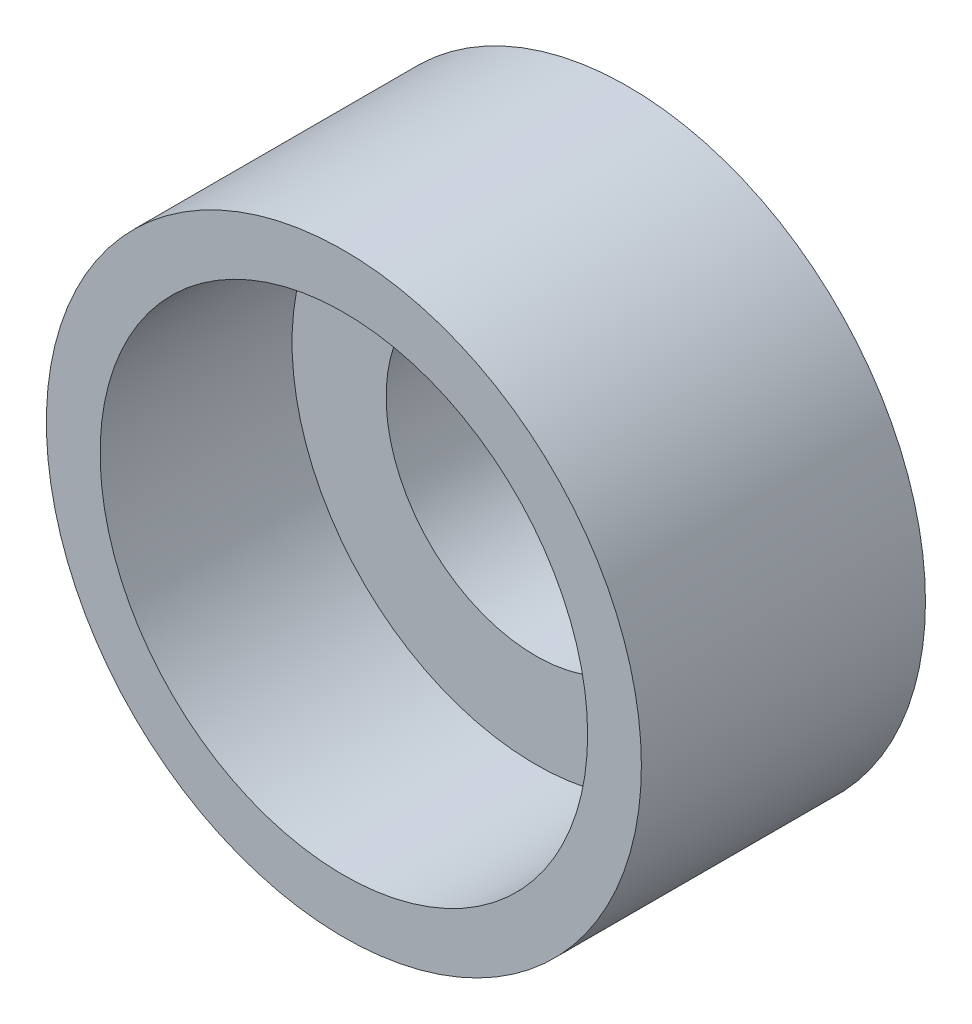
SolidWorks part; units mm, degrees
ref_plane "Front Plane" through (0, 0, 0) normal (1, 0, 0) x (0, 1, 0)
ref_plane "Top Plane" through (0, 0, 0) normal (0, 0, 1) x (0, 1, 0)
ref_plane "Right Plane" through (0, 0, 0) normal (0, 1, 0) x (-1, 0, 0)
ref_axis "x axis" through (-88.99, 0, 0) along (1, 0, 0)
ref_axis "y xxis" through (0, 88.99, 0) along (0, -1, 0)
ref_axis "z axis" through (0, 0, 55) along (0, 0, -1)
sketch "Sketch1" plane through (0, 0, 0) normal (0, 0, 1) x (0, 1, 0)
  circle A0 centre (0, 0) radius 1.95
  circle A1 centre (0, 0) radius 3.875
  circle A2 centre (0, 0) radius 3.175 construction
  dimension "D1" = 6.35
  dimension "D2" = 0.7
  dimension "D3" = 3.9
extrude "Boss-Extrude1" add sketch "Sketch1" along normal blind 1.2
sketch "Sketch2" plane through (0, 0, 1.2) normal (0, 0, 1) x (1, 0, 0)
  circle A0 centre (0, 0) radius 3.175
  circle A1 centre (0, 0) radius 3.875
  circle A2 centre (0, 0) radius 3.175 construction
  circle A3 centre (0, 0) radius 3.875 construction
extrude "Boss-Extrude2" add sketch "Sketch2" along normal blind 2.5
